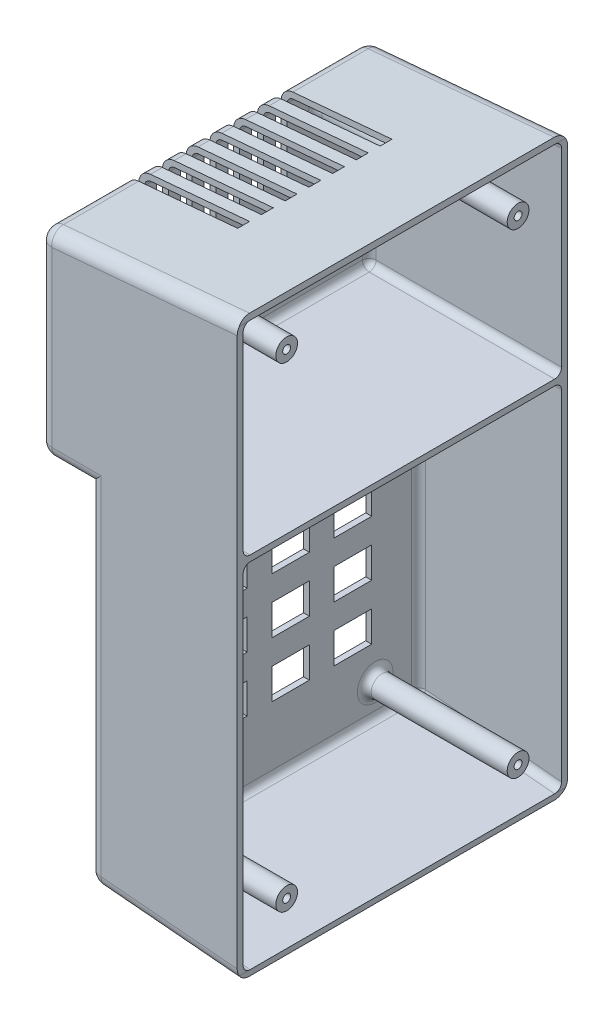
SolidWorks part; units mm, degrees
ref_plane "Front Plane" through (0, 0, 0) normal (0, 0, 1) x (1, 0, 0)
ref_plane "Top Plane" through (0, 0, 0) normal (0, 1, 0) x (1, 0, 0)
ref_plane "Right Plane" through (0, 0, 0) normal (1, 0, 0) x (0, 0, -1)
sketch "Sketch1" plane through (0, 0, 0) normal (0, 0, 1) x (1, 0, 0)
  line L0 (8.0503, 31.7182) -> (-42.7497, 27.2738)
  line L1 (-42.7497, 27.2738) -> (-42.7497, -23.5262)
  line L2 (-42.7497, 27.2738) -> (-10.649, 27.2738) construction
  line L3 (-42.7497, -23.5262) -> (-30.0497, -23.5262)
  line L4 (-30.0497, -23.5262) -> (-30.0497, -112.4262)
  line L5 (-30.0497, -112.4262) -> (8.0503, -115.7595)
  line L6 (-30.0497, -112.4262) -> (6.5765, -112.4262) construction
  line L7 (8.1831, 30.2) -> (-41.2257, 25.8773)
  line L8 (-41.2257, 25.8773) -> (-41.2257, -22.0022)
  line L9 (-41.2257, -22.0022) -> (-28.5257, -22.0022)
  line L10 (-28.5257, -23.5262) -> (-28.5257, -111.0297)
  line L11 (-28.5257, -111.0297) -> (8.1831, -114.2413)
  line L12 (-28.5257, -22.0022) -> (8.1831, -22.0022)
  line L13 (-28.5257, -23.5262) -> (8.1831, -23.5262)
  line L14 (8.1831, -23.5262) -> (8.1831, -22.0022)
  line L15 (-28.5257, -22.0022) -> (-28.5257, -111.0297) construction
  line L16 (8.0503, 31.7182) -> (8.1831, 30.2)
  line L17 (8.1831, -114.2413) -> (8.0503, -115.7595)
  dimension "D1" = 50.8
  dimension "D2" = 5
  dimension "D3" = 50.8
  dimension "D4" = 12.7
  dimension "D5" = 139.7
  dimension "D6" = 5
  dimension "D7" = 50.8
  dimension "D8" = 1.524
extrude "Boss-Extrude1" add sketch "Sketch1" along normal blind 84.836 contours L1 L3 L4 L5 L17 L11 L10 L13 L14 L12 L9 L8 L7 L16 L0
sketch "Sketch2" plane through (8.1831, 0, 0) normal (1, 0, 0) x (0, 0, -1)
  line L2 (-84.836, 31.7182) -> (-83.312, 31.7182)
  line L4 (-84.836, -22.0022) -> (-83.312, -22.0022)
  line L9 (0, -22.0022) -> (-1.524, -22.0022)
  line L13 (-84.836, -22.0022) -> (0, -22.0022) construction
  line L22 (0, 31.7182) -> (0, -115.7595)
  line L23 (-1.524, 31.7182) -> (-1.524, -115.7595)
  line L24 (-84.836, 31.7182) -> (0, 31.7182) construction
  line L25 (-84.836, -115.7595) -> (0, -115.7595) construction
  line L26 (-1.524, -115.7595) -> (0, -115.7595)
  line L27 (-1.524, 31.7182) -> (0, 31.7182)
  line L28 (-84.836, 31.7182) -> (-84.836, -115.7595)
  line L29 (-83.312, 31.7182) -> (-83.312, -115.7595)
  line L30 (-84.836, -115.7595) -> (-83.312, -115.7595)
  dimension "D1" = 1.524
  dimension "D2" = 1.524
extrude "Boss-Extrude3" add sketch "Sketch2" against normal up to surface (49.4088 mm away) contours L28 L30 L29 L2 up to face at (-41.2257, 1.9375, 42.418)
sketch "Sketch3" plane through (0, 0, 83.312) normal (0, 0, -1) x (-1, 0, 0)
  line L0 (-8.0503, -115.7595) -> (30.0497, -112.4262)
  line L1 (30.0497, -112.4262) -> (30.0497, -23.5262)
  line L2 (30.0497, -23.5262) -> (42.7497, -23.5262)
  line L3 (42.7497, -23.5262) -> (42.7497, 27.2738)
  line L4 (42.7497, 27.2738) -> (-8.0503, 31.7182)
  line L5 (-8.0503, 31.7182) -> (-8.1831, 30.2)
  line L6 (-8.1831, 30.2) -> (-14.1571, 30.7227)
  line L7 (-14.1571, 30.7227) -> (-14.1571, 64.8964)
  line L8 (-14.1571, 64.8964) -> (63.9433, 64.8964)
  line L9 (63.9433, 64.8964) -> (63.9433, -137.0767)
  line L10 (63.9433, -137.0767) -> (-11.6951, -137.0767)
  line L11 (-11.6951, -137.0767) -> (-11.6951, -114.0929)
  line L12 (-11.6951, -114.0929) -> (-8.1831, -114.2413)
  line L13 (-8.1831, -114.2413) -> (-8.0503, -115.7595)
extrude "Cut-Extrude1" cut sketch "Sketch3" against normal blind 84.836
extrude "Boss-Extrude4" add sketch "Sketch2<5>" against normal up to surface (49.4088 mm away) contours L22 L26 L23 L27 up to face at (-41.2257, 1.9375, 41.656)
sketch "Sketch2<5>" plane through (8.1831, 0, 0) normal (1, 0, 0) x (0, 0, -1) same geometry as "Sketch2"
extrude "Cut-Extrude2" cut sketch "Sketch3<2>" along normal blind 137.922 contours L10 L11 L12 L13 L0 L1 L2 L3 L4 L5 L6 L7 L8 L9
sketch "Sketch3<2>" plane through (0, 0, 83.312) normal (0, 0, -1) x (-1, 0, 0) same geometry as "Sketch3"
sketch "Sketch4" plane through (-41.2257, 0, 0) normal (1, 0, 0) x (0, 0, -1)
  line L0 (-72.136, 19.0182) -> (-12.7, 19.0182) construction
  line L1 (-84.836, 31.7182) -> (0, 31.7182) construction
  line L2 (0, -114.2413) -> (0, 30.2) construction
  line L3 (-84.836, -114.2413) -> (-84.836, 30.2) construction
  circle A0 centre (-12.7, 19.0182) radius 2.794
  circle A1 centre (-72.136, 19.0182) radius 2.794
  circle A2 centre (-72.136, 19.0182) radius 1.016
  circle A3 centre (-12.7, 19.0182) radius 1.016
  dimension "D1" = 5.588
  dimension "D2" = 5.588
  dimension "D3" = 12.7
  dimension "D4" = 12.7
  dimension "D5" = 12.7
  dimension "D6" = 2.032
  dimension "D7" = 2.032
sketch "Sketch5" plane through (-28.5257, 0, 0) normal (1, 0, 0) x (0, 0, -1)
  line L0 (-72.136, -103.0595) -> (-12.7, -103.0595) construction
  line L1 (-42.418, -115.7595) -> (-42.418, -22.0022) construction
  line L2 (-84.836, -115.7595) -> (0, -115.7595) construction
  line L3 (-83.312, -22.0022) -> (-1.524, -22.0022) construction
  circle A0 centre (-72.136, -103.0595) radius 2.794
  circle A1 centre (-12.7, -103.0595) radius 2.794
  circle A2 centre (-72.136, -103.0595) radius 1.016
  circle A3 centre (-12.7, -103.0595) radius 1.016
  dimension "D1" = 5.588
  dimension "D2" = 5.588
  dimension "D5" = 12.7
  dimension "D6" = 2.032
  dimension "D7" = 2.032
  dimension "D3" = 29.718
  dimension "D4" = 29.718
extrude "Boss-Extrude5" add sketch "Sketch5" along normal up to surface (36.7088 mm away) up to face at (8.1831, -35.6019, 42.418)
extrude "Boss-Extrude6" add sketch "Sketch4" along normal up to surface (49.4088 mm away) up to face at (8.1831, -35.6019, 42.418)
sketch "Sketch6" plane through (-28.5257, 0, 0) normal (1, 0, 0) x (0, 0, -1)
  line L0 (-84.836, -115.7595) -> (0, -115.7595) construction
  line L1 (-55.245, -86.2955) -> (-45.593, -86.2955)
  line L2 (-55.245, -86.2955) -> (-55.245, -94.1695)
  line L3 (-55.245, -94.1695) -> (-45.593, -94.1695)
  line L4 (-45.593, -86.2955) -> (-45.593, -94.1695)
  line L5 (-42.418, -115.7595) -> (-42.418, -22.0022) construction
  line L6 (-83.312, -22.0022) -> (-1.524, -22.0022) construction
  line L7 (-39.243, -86.2955) -> (-29.591, -86.2955)
  line L8 (-39.243, -86.2955) -> (-39.243, -94.1695)
  line L9 (-39.243, -94.1695) -> (-29.591, -94.1695)
  line L10 (-29.591, -86.2955) -> (-29.591, -94.1695)
  line L11 (-23.241, -86.2955) -> (-13.589, -86.2955)
  line L12 (-23.241, -86.2955) -> (-23.241, -94.1695)
  line L13 (-23.241, -94.1695) -> (-13.589, -94.1695)
  line L14 (-13.589, -86.2955) -> (-13.589, -94.1695)
  line L15 (-39.243, -72.0715) -> (-29.591, -72.0715)
  line L16 (-39.243, -72.0715) -> (-39.243, -79.9455)
  line L17 (-39.243, -79.9455) -> (-29.591, -79.9455)
  line L18 (-29.591, -72.0715) -> (-29.591, -79.9455)
  line L19 (-23.241, -72.0715) -> (-13.589, -72.0715)
  line L20 (-23.241, -72.0715) -> (-23.241, -79.9455)
  line L21 (-23.241, -79.9455) -> (-13.589, -79.9455)
  line L22 (-13.589, -72.0715) -> (-13.589, -79.9455)
  line L23 (-39.243, -57.8475) -> (-29.591, -57.8475)
  line L24 (-39.243, -57.8475) -> (-39.243, -65.7215)
  line L25 (-39.243, -65.7215) -> (-29.591, -65.7215)
  line L26 (-29.591, -57.8475) -> (-29.591, -65.7215)
  line L27 (-23.241, -57.8475) -> (-13.589, -57.8475)
  line L28 (-23.241, -57.8475) -> (-23.241, -65.7215)
  line L29 (-23.241, -65.7215) -> (-13.589, -65.7215)
  line L30 (-13.589, -57.8475) -> (-13.589, -65.7215)
  line L31 (-55.245, -72.0715) -> (-45.593, -72.0715)
  line L32 (-55.245, -72.0715) -> (-55.245, -79.9455)
  line L33 (-55.245, -79.9455) -> (-45.593, -79.9455)
  line L34 (-45.593, -72.0715) -> (-45.593, -79.9455)
  line L35 (-55.245, -57.8475) -> (-45.593, -57.8475)
  line L36 (-55.245, -57.8475) -> (-55.245, -65.7215)
  line L37 (-55.245, -65.7215) -> (-45.593, -65.7215)
  line L38 (-45.593, -57.8475) -> (-45.593, -65.7215)
  line L52 (-61.595, -86.2955) -> (-71.247, -86.2955)
  line L53 (-61.595, -86.2955) -> (-61.595, -94.1695)
  line L54 (-61.595, -94.1695) -> (-71.247, -94.1695)
  line L55 (-71.247, -86.2955) -> (-71.247, -94.1695)
  line L56 (-61.595, -72.0715) -> (-71.247, -72.0715)
  line L57 (-61.595, -72.0715) -> (-61.595, -79.9455)
  line L58 (-61.595, -79.9455) -> (-71.247, -79.9455)
  line L59 (-71.247, -72.0715) -> (-71.247, -79.9455)
  line L60 (-61.595, -57.8475) -> (-71.247, -57.8475)
  line L61 (-61.595, -57.8475) -> (-61.595, -65.7215)
  line L62 (-61.595, -65.7215) -> (-71.247, -65.7215)
  line L63 (-71.247, -57.8475) -> (-71.247, -65.7215)
  dimension "D1" = 7.874
  dimension "D2" = 21.59
  dimension "D3" = 9.652
  dimension "D4" = 3.175
  dimension "D7" = 9.652
  dimension "D8" = 6.35
  dimension "D5" = 3
  dimension "D6" = 3
extrude "Cut-Extrude3" cut sketch "Sketch6" against normal blind 137.922
fillet "Fillet1" radius 3.302 13 edges at (-17.3497, 29.496, 0) (-10.9997, -114.0929, 84.836) (-10.9997, -114.0929, 0) (-30.0497, -112.4262, 42.418) (-30.0497, -67.9762, 0) (-36.3997, -23.5262, 0) (-42.7497, 1.8738, 0) (-42.7497, -23.5262, 42.418) (-36.3997, -23.5262, 84.836) (-30.0497, -67.9762, 84.836) (-42.7497, 1.8738, 84.836) (-42.7497, 27.2738, 42.418) (-17.3497, 29.496, 84.836)
fillet "Fillet2" radius 1.778 19 edges at (-41.2257, 19.0182, 69.342) (-41.2257, 19.0182, 9.906) (-28.5257, -103.0595, 9.906) (-28.5257, -103.0595, 69.342) (-10.1713, -112.6355, 83.312) (-10.1713, -112.6355, 1.524) (-10.1713, -23.5262, 83.312) (-10.1713, -23.5262, 1.524) (-28.5257, -23.5262, 42.418) (-28.5257, -67.278, 1.524) (-28.5257, -67.278, 83.312) (-28.5257, -111.0297, 42.418) (-41.2257, 25.8773, 42.418) (-16.5213, 28.0386, 1.524) (-16.5213, 28.0386, 83.312) (-16.5213, -22.0022, 83.312) (-41.2257, -22.0022, 42.418) (-16.5213, -22.0022, 1.524) (-41.2257, 1.9375, 1.524)
sketch "Sketch7" plane through (-42.7497, 0, 0) normal (-1, 0, 0) x (0, 0, 1)
  line L0 (42.418, 31.7182) -> (42.418, -20.2242) construction
  line L1 (81.534, 31.7182) -> (3.302, 31.7182) construction
  line L2 (3.302, -20.2242) -> (81.534, -20.2242) construction
  line L3 (81.534, 24.248) -> (3.302, 24.248) construction
  line L4 (40.894, 42.1779) -> (43.942, 42.1779)
  line L5 (40.894, 42.1779) -> (40.894, 6.3182)
  line L6 (40.894, 6.3182) -> (43.942, 6.3182)
  line L7 (43.942, 42.1779) -> (43.942, 6.3182)
  line L8 (40.894, 42.1779) -> (43.942, 6.3182) construction
  line L9 (40.894, 6.3182) -> (43.942, 42.1779) construction
  line L10 (50.038, 42.1779) -> (50.038, 6.3182)
  line L11 (46.99, 42.1779) -> (50.038, 42.1779)
  line L12 (46.99, 42.1779) -> (46.99, 6.3182)
  line L13 (46.99, 6.3182) -> (50.038, 6.3182)
  line L14 (56.134, 42.1779) -> (56.134, 6.3182)
  line L15 (53.086, 42.1779) -> (56.134, 42.1779)
  line L16 (53.086, 42.1779) -> (53.086, 6.3182)
  line L17 (53.086, 6.3182) -> (56.134, 6.3182)
  line L18 (62.23, 42.1779) -> (62.23, 6.3182)
  line L19 (59.182, 42.1779) -> (62.23, 42.1779)
  line L20 (59.182, 42.1779) -> (59.182, 6.3182)
  line L21 (59.182, 6.3182) -> (62.23, 6.3182)
  line L22 (34.798, 42.1779) -> (34.798, 6.3182)
  line L23 (37.846, 42.1779) -> (37.846, 6.3182)
  line L24 (34.798, 6.3182) -> (37.846, 6.3182)
  line L25 (34.798, 42.1779) -> (37.846, 42.1779)
  line L26 (28.702, 42.1779) -> (28.702, 6.3182)
  line L27 (31.75, 42.1779) -> (31.75, 6.3182)
  line L28 (28.702, 6.3182) -> (31.75, 6.3182)
  line L29 (28.702, 42.1779) -> (31.75, 42.1779)
  line L30 (22.606, 42.1779) -> (22.606, 6.3182)
  line L31 (25.654, 42.1779) -> (25.654, 6.3182)
  line L32 (22.606, 6.3182) -> (25.654, 6.3182)
  line L33 (22.606, 42.1779) -> (25.654, 42.1779)
  point P6 (42.418, 24.248)
  dimension "D1" = 3.048
  dimension "D2" = 25.4
  dimension "D3" = 4
  dimension "D4" = 4
extrude "Cut-Extrude4" cut sketch "Sketch7" against normal blind 28.448
